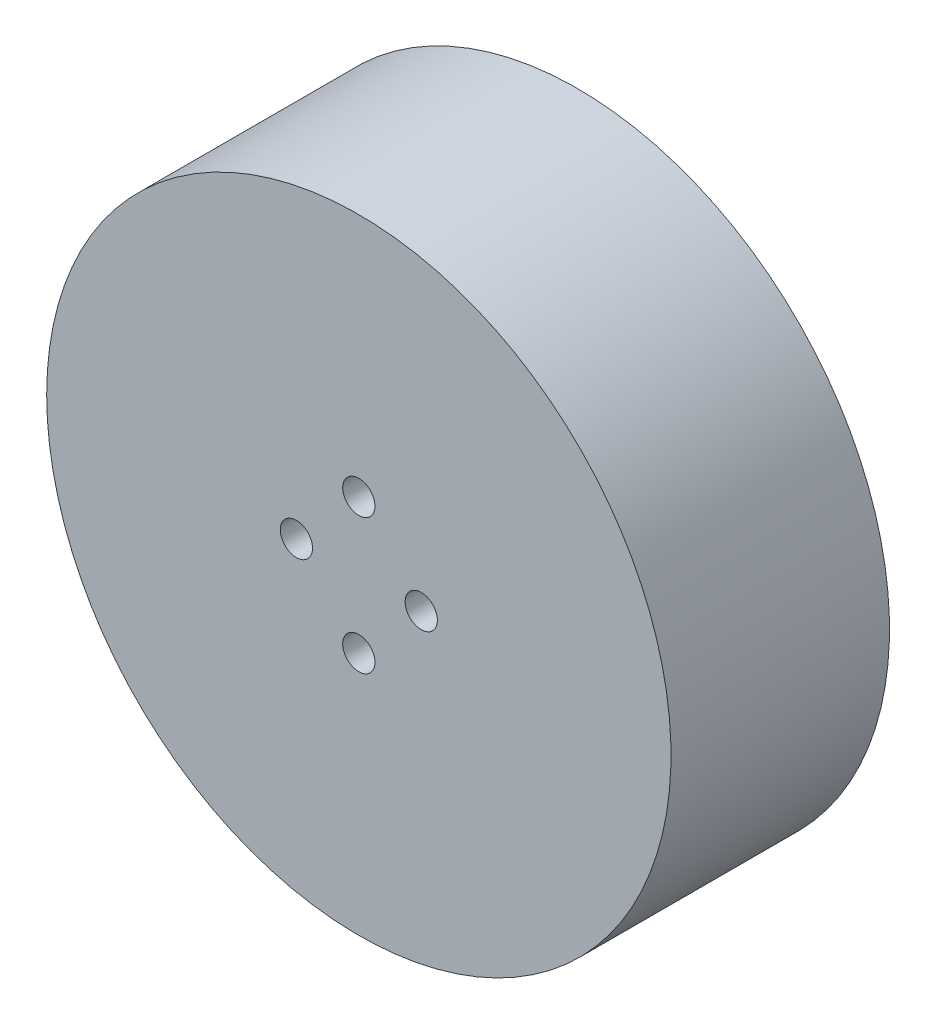
SolidWorks part; units mm, degrees
ref_plane "Front Plane" through (0, 0, 0) normal (0, 0, 1) x (1, 0, 0)
ref_plane "Top Plane" through (0, 0, 0) normal (0, 1, 0) x (1, 0, 0)
ref_plane "Right Plane" through (0, 0, 0) normal (1, 0, 0) x (0, 0, -1)
sketch "Sketch1" plane through (0, 0, 0) normal (0, 0, 1) x (1, 0, 0)
  circle A0 centre (0, 0) radius 30
  dimension "D1" = 60
extrude "Boss-Extrude1" add sketch "Sketch1" along normal mid plane 21
sketch "Sketch2" plane through (0, 0, 10.5) normal (0, 0, 1) x (1, 0, 0)
  line L1 (0, -6.5) -> (6, 0) construction
  line L2 (0, -6.5) -> (-6, 0) construction
  line L3 (-6, 0) -> (0, 6.5) construction
  line L4 (6, 0) -> (0, 6.5) construction
  line L5 (0, -6.5) -> (0, 6.5) construction
  line L6 (-6, 0) -> (6, 0) construction
  circle A0 centre (-6, 0) radius 1.55
  circle A4 centre (0, 6.5) radius 1.55
  circle A5 centre (6, 0) radius 1.55
  circle A6 centre (0, -6.5) radius 1.55
  point P10 (4.8837, -4.7762)
  point P11 (0, 0)
  point P12 (0, 0)
  dimension "D2" = 3.1
  dimension "D1" = 13
  dimension "D3" = 12
extrude "Cut-Extrude1" cut sketch "Sketch2" against normal blind 10
sketch "Sketch3" plane through (0, 0, -10.5) normal (0, 0, -1) x (-1, 0, 0)
  circle A0 centre (0, 0) radius 21
  dimension "D1" = 42
extrude "Cut-Extrude2" cut sketch "Sketch3" against normal blind 17
